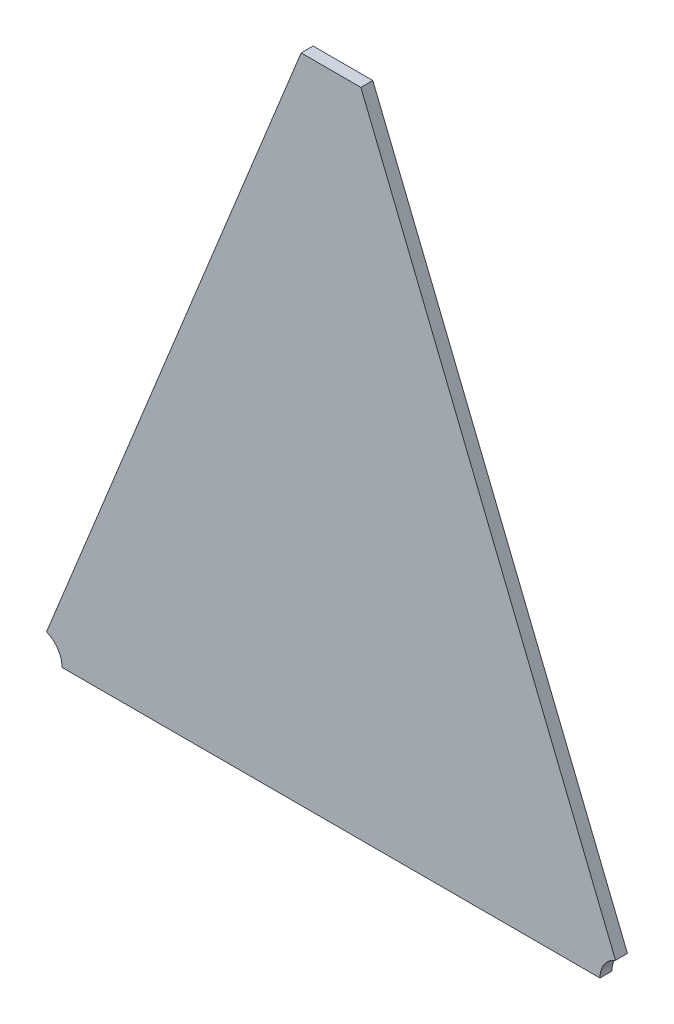
SolidWorks part; units mm, degrees
ref_plane "Front Plane" through (0, 0, 0) normal (0, 0, 1) x (1, 0, 0)
ref_plane "Top Plane" through (0, 0, 0) normal (0, 1, 0) x (1, 0, 0)
ref_plane "Right Plane" through (0, 0, 0) normal (1, 0, 0) x (0, 0, -1)
sketch "Sketch2" plane through (0, 0, 0) normal (0, 0, 1) x (1, 0, 0)
  line L0 (-189.7401, 245.3834) -> (-358.1285, -170.4146)
  line L1 (-358.1285, -170.4146) -> (16.7755, -170.4146)
  line L2 (16.7755, -170.4146) -> (-151.6401, 245.3834)
  line L4 (-189.7401, 245.3834) -> (-151.6401, 245.3834)
  point P2 (-162.0864, 241.1535)
  point P5 (-175.2183, 241.8349)
  point P6 (-129.4107, 241.652)
  point P7 (-139.2066, 244.5257)
  point P8 (-154.3191, 243.1519)
  point P9 (-158.9446, 242)
  point P10 (-184.3187, 244.1958)
  point P11 (-188.9759, 243.5305)
  point P12 (-189.7401, 245.3834)
  dimension "D1" = 415.798
  dimension "D2" = 415.798
  dimension "D3" = 67.95
  dimension "D4" = 38.1
  dimension "D5" = 374.904
extrude "Boss-Extrude1" add sketch "Sketch2" along normal blind 7.62 contours L0 L1 L2 L4
sketch "Sketch5" plane through (0, 0, 0) normal (0, 0, -1) x (-1, 0, 0)
  circle A0 centre (358.1285, -170.4146) radius 15.875
  dimension "D1" = 31.75
extrude "Cut-Extrude2" cut sketch "Sketch5" against normal blind 50.8
sketch "Sketch6" plane through (0, 0, 0) normal (0, 0, -1) x (-1, 0, 0)
  circle A0 centre (-16.7755, -170.4146) radius 15.875
  dimension "D1" = 31.75
extrude "Cut-Extrude3" cut sketch "Sketch6" against normal blind 50.8 contours A0
